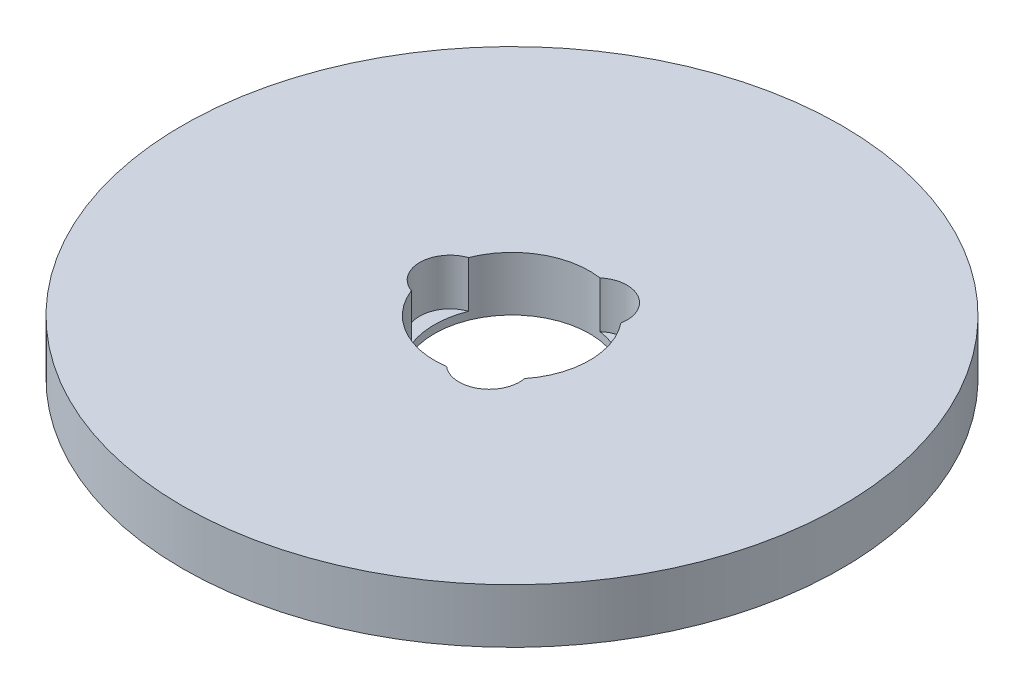
SolidWorks part; units mm, degrees
ref_plane "Front Plane" through (0, 0, 0) normal (0, 0, 1) x (1, 0, 0)
ref_plane "Top Plane" through (0, 0, 0) normal (0, 1, 0) x (1, 0, 0)
ref_plane "Right Plane" through (0, 0, 0) normal (1, 0, 0) x (0, 0, -1)
sketch "Sketch1" plane through (0, 0, 0) normal (0, 1, 0) x (1, 0, 0)
  circle A0 centre (0, 0) radius 42.5
  dimension "FLANGE_OD" = 85
extrude "Boss-Extrude1" add sketch "Sketch1" along normal blind 7
sketch "Sketch2" plane through (0, 0, 0) normal (0, 1, 0) x (1, 0, 0)
  circle A0 centre (0, 0) radius 10
  dimension "BORE_D" = 20
extrude "Cut-Extrude1" cut sketch "Sketch2" along normal through all
sketch "Sketch3" plane through (0, 7, 0) normal (0, 1, 0) x (1, 0, 0)
  circle A0 centre (0, 0) radius 7.9887 construction
  circle A1 centre (-7.9887, 0) radius 3.9115
  dimension "BOLT_D" = 7.823
  dimension "BOLT_PCD" = 15.9775
extrude "Cut-Extrude2" cut sketch "Sketch3" against normal blind 6.001
pattern_circular "CirPattern1" count 3 over 360 about axis through (0, 0, 0) along (0, 1, 0) of "Cut-Extrude2"
